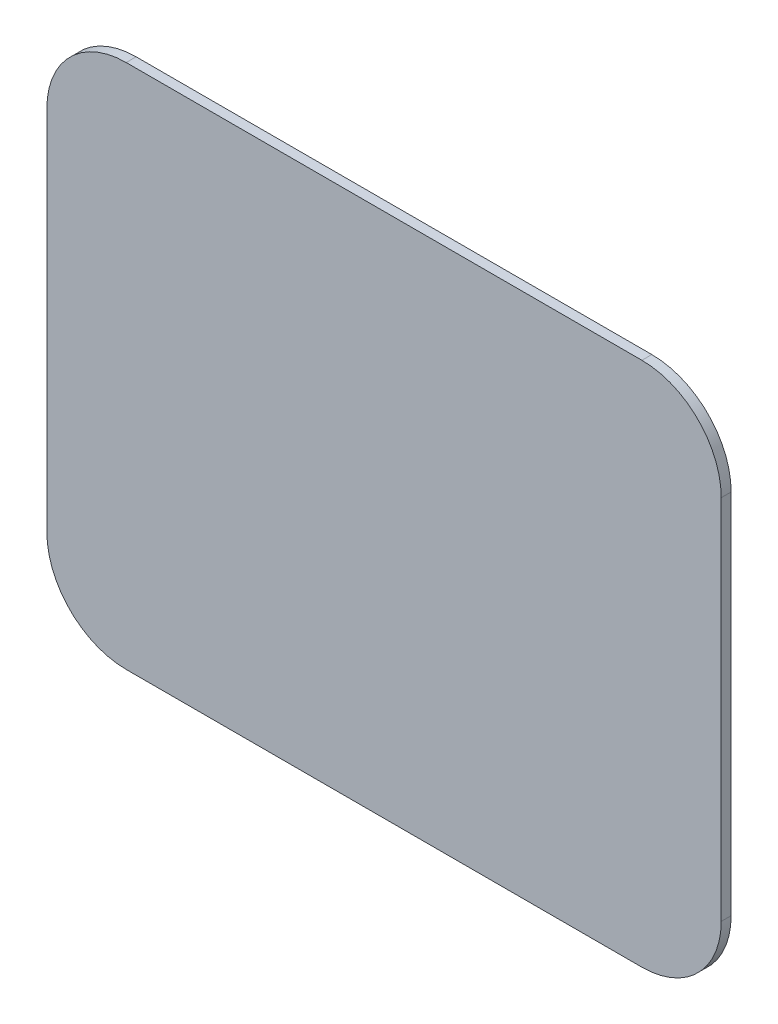
SolidWorks part; units mm, degrees
ref_plane "Plan de face" through (0, 0, 0) normal (0, 0, 1) x (1, 0, 0)
ref_plane "Plan de dessus" through (0, 0, 0) normal (0, 1, 0) x (1, 0, 0)
ref_plane "Plan de droite" through (0, 0, 0) normal (1, 0, 0) x (0, 0, -1)
sketch "Esquisse1" plane through (0, 0, 0) normal (0, 0, 1) x (1, 0, 0)
  line L1 (-340, -265) -> (340, -265)
  line L2 (-340, -265) -> (-340, 265)
  line L3 (-340, 265) -> (340, 265)
  line L4 (340, -265) -> (340, 265)
  line L5 (-340, -265) -> (340, 265) construction
  line L6 (-340, 265) -> (340, -265) construction
  point P0 (0, 0)
  dimension "D1" = 680
  dimension "D2" = 530
extrude "Boss.-Extru.1" add sketch "Esquisse1" along normal blind 10
sketch "Esquisse9" plane through (0, 0, 10) normal (0, 0, 1) x (1, 0, 0)
  line L0 (-265, 265) -> (-265, 195) construction
  line L1 (340, 265) -> (-340, 265) construction
  line L2 (-265, 195) -> (-340, 195) construction
  line L3 (-340, 265) -> (-340, -265) construction
  line L4 (-265, 195) -> (-265, 70) construction
  line L5 (-265, 70) -> (-265, 51.3985) construction
  line L6 (-265, 70) -> (-265, -55) construction
  circle A0 centre (-265, 195) radius 3.7807
  circle A1 centre (-265, 70) radius 1.8072
  circle A2 centre (-265, -55) radius 2.9752
  dimension "D1" = 70
  dimension "D2" = 75
  dimension "D3" = 125
  dimension "D4" = 125
fillet "Congé1" radius 80 4 edges at (-340, 265, 5) (340, -265, 5) (340, 265, 5) (-340, -265, 5)
